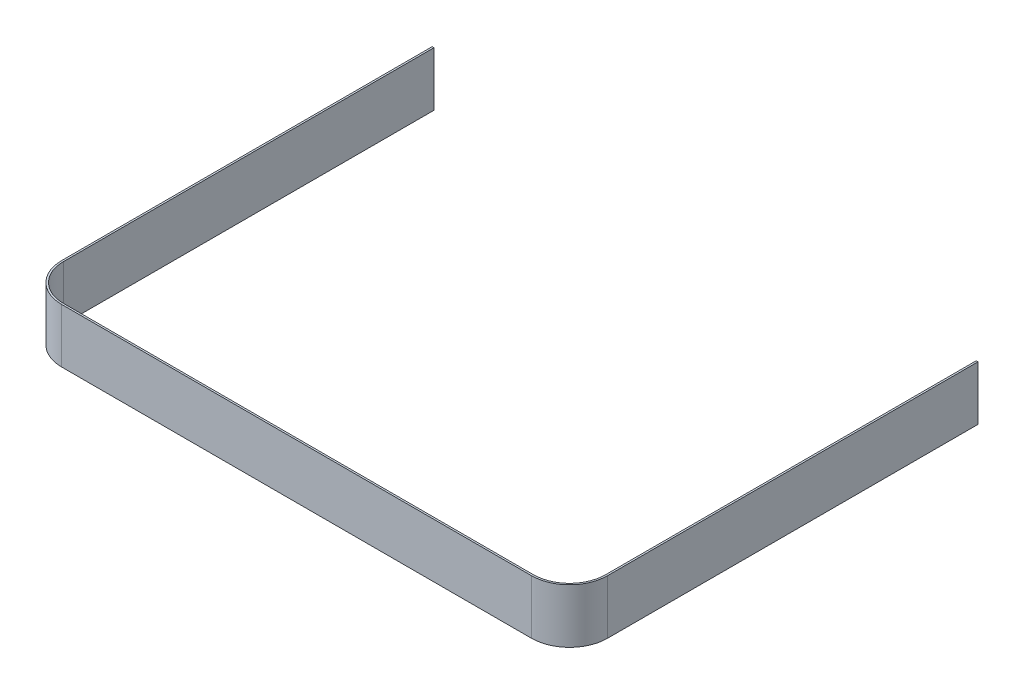
SolidWorks part; units mm, degrees
ref_plane "Ebene vorne" through (0, 0, 0) normal (0, 0, 1) x (1, 0, 0)
ref_plane "Ebene oben" through (0, 0, 0) normal (0, 1, 0) x (1, 0, 0)
ref_plane "Ebene rechts" through (0, 0, 0) normal (1, 0, 0) x (0, 0, -1)
sketch "Skizze1" plane through (0, 0, 0) normal (0, -1, 0) x (1, 0, 0)
  line L0 (0, 75) -> (130, 75)
  line L1 (-130, 75) -> (130, 75) construction
  line L2 (150, 55) -> (150, -150)
  arc A0 (130, 75) -> (150, 55) centre (130, 55) cw
extrude "Linear-Austragen-Dünn1" add sketch "Skizze1" against normal blind 30 thin thin type one direction reverse wall 1
mirror "Spiegeln1" about plane through (0, 30, 75) normal (1, 0, 0) of "Linear-Austragen-Dünn1"
